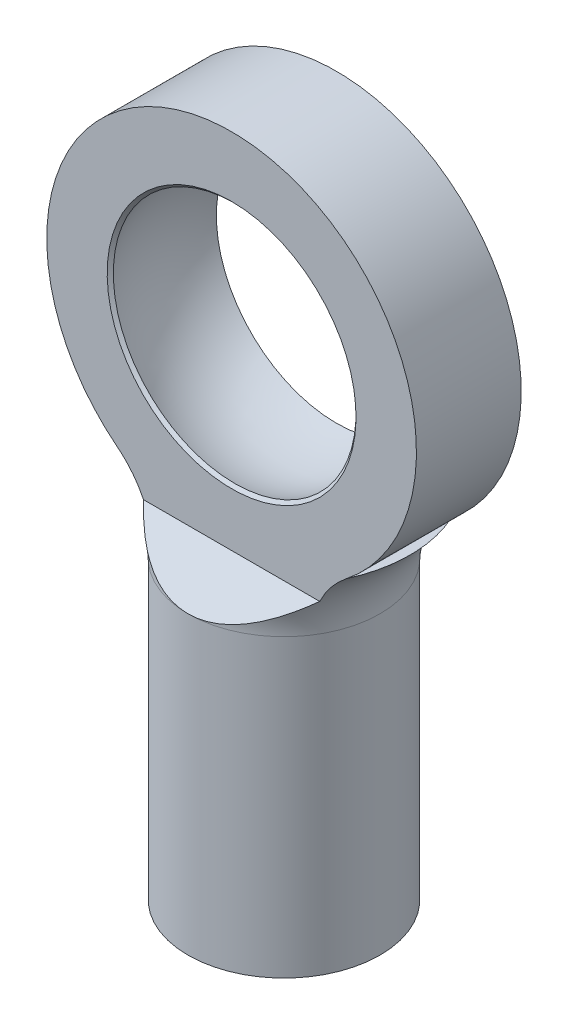
SolidWorks part; units mm, degrees
ref_plane "Top Plane" through (0, 0, 0) normal (0, 0, 1) x (1, 0, 0)
ref_plane "Front Plane" through (0, 0, 0) normal (0, 1, 0) x (1, 0, 0)
ref_plane "Right Plane" through (0, 0, 0) normal (1, 0, 0) x (0, 0, -1)
sketch "Sketch1" plane through (0, 0, 0) normal (0, 0, 1) x (1, 0, 0)
  line L0 (0, 0) -> (0, -6.5043) construction
  line L3 (0, -14.5) -> (2.75, -14.5)
  line L4 (2.75, -6.0363) -> (2.75, -14.5)
  line L5 (0, 5.5) -> (0, -14.5)
  arc A0 (3.6094, -4.15) -> (0, 5.5) centre (0, 0) ccw
  arc A1 (3.6094, -4.15) -> (2.75, -6.0363) centre (5.25, -6.0363) ccw
  point P0 (0, 0)
  point P5 (0, 0)
  point P6 (0, 0)
  point P9 (0, 0)
  point P12 (0, 0)
  point P15 (0, 0)
  point P16 (0, 13.4817)
  point P17 (0, 5.4888)
  dimension "D1" = 11
  dimension "D3" = 2.5
  dimension "D2" = 14.5
  dimension "D4" = 2.75
revolve "Revolve1" add sketch "Sketch1" angle 360 about L0
sketch "Sketch2" plane through (0, 0, 0) normal (1, 0, 0) x (0, 0, -1)
  line L0 (-6.5, -5.0932) -> (-2.75, -6.0363)
  line L1 (-6.5, 5.9068) -> (-1.5, 5.9068)
  line L2 (-6.5, 5.9068) -> (-6.5, -5.0932)
  line L4 (-1.5, 5.9068) -> (-1.5, -5.0932)
  line L5 (-2.75, -6.0363) -> (-1.5, -5.0932)
  line L10 (6.5, 5.9068) -> (6.5, -5.0932)
  line L11 (6.5, 5.9068) -> (1.5, 5.9068)
  line L12 (1.5, 5.9068) -> (1.5, -5.0932)
  line L13 (-3.6094, -4.15) -> (3.6094, -4.15) construction
  line L14 (-2.75, -6.0363) -> (2.75, -6.0363) construction
  line L15 (-3.6094, -4.15) -> (3.6094, -4.15) construction
  line L16 (-2.75, -6.0363) -> (2.75, -6.0363) construction
  line L17 (0, -4.15) -> (0, -6.0363) construction
  line L18 (2.75, -6.0363) -> (1.5, -5.0932)
  line L19 (6.5, -5.0932) -> (2.75, -6.0363)
  point P4 (0, -5.0932)
  dimension "D1" = 5
  dimension "D2" = 1.5
  dimension "D3" = 11
extrude "Cut-Extrude1" cut sketch "Sketch2" against normal through all both and the other way through all
sketch "Sketch3" plane through (0, 0, 0) normal (0, 0, 1) x (1, 0, 0)
  arc A1 (3.2829, -4.15) -> (-3.2829, -4.15) centre (0, 0) ccw construction
  arc A2 (3.2829, -4.15) -> (-3.2829, -4.15) centre (0, 0) ccw construction
  circle A3 centre (0, 0) radius 3
  dimension "D1" = 6
extrude "Cut-Extrude2" cut sketch "Sketch3" against normal through all both and the other way through all
sketch "Sketch5" plane through (0, 0, 0) normal (0, 0, 1) x (1, 0, 0)
  line L0 (0, 3.75) -> (0, -3.75)
  arc A1 (0, -3.75) -> (0, 3.75) centre (0, 0) ccw
  circle A2 centre (0, 0) radius 3 construction
  dimension "D1" = 7.5
revolve "Cut-Revolve2" cut sketch "Sketch5" angle 360 about L0
chamfer "Chamfer1" distance 0.125 angle 45 1 edges at (0, 3.4369, 1.5) first distance on face at (0, 3.4369, 1.5)
sketch "Sketch6" plane through (0, 0, 1.5) normal (0, 0, 1) x (1, 0, 0)
  line L2 (-3.6094, -4.15) -> (-3.2829, -4.15)
  line L3 (3.2829, -4.15) -> (3.6094, -4.15)
  arc A3 (3.6094, -4.15) -> (-3.6094, -4.15) centre (0, 0) ccw construction
  arc A4 (3.6094, -4.15) -> (-3.6094, -4.15) centre (0, 0) ccw
  arc A5 (3.2829, -4.15) -> (-3.2829, -4.15) centre (0, 0) ccw construction
  arc A6 (3.2829, -4.15) -> (-3.2829, -4.15) centre (0, 0) ccw
extrude "Cut-Extrude3" cut sketch "Sketch6" against normal through all both
sketch "Sketch7" plane through (0, -14.5, 0) normal (0, -1, 0) x (1, 0, 0)
  circle A0 centre (0, 0) radius 1.5
  dimension "D1" = 3
extrude "Cut-Extrude4" cut sketch "Sketch7" against normal blind 5
